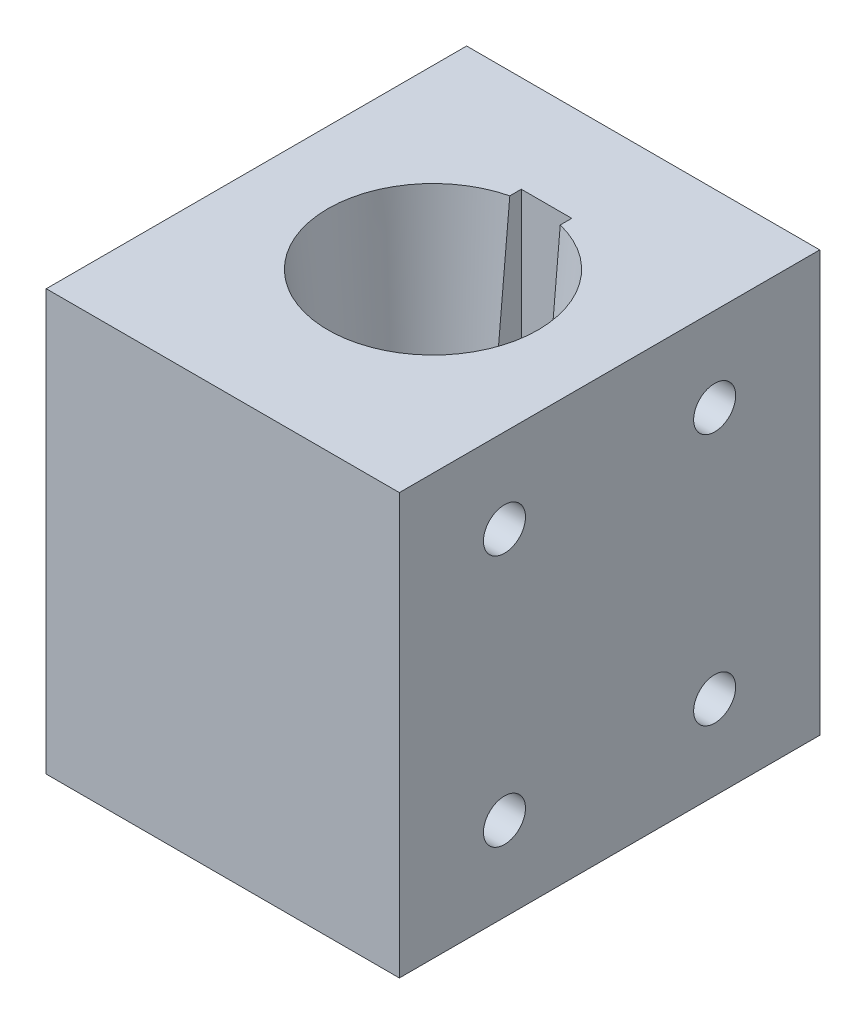
SolidWorks part; units mm, degrees
material "PA38 (3.3206)"
ref_plane "Płaszczyzna przednia" through (0, 0, 0) normal (0, 0, 1) x (1, 0, 0)
ref_plane "Płaszczyzna górna" through (0, 0, 0) normal (0, 1, 0) x (1, 0, 0)
ref_plane "Płaszczyzna prawa" through (0, 0, 0) normal (1, 0, 0) x (0, 0, -1)
sketch "Szkic6" plane through (0, 0, 0) normal (0, 1, 0) x (1, 0, 0)
  line L1 (21, -25) -> (-21, -25)
  line L2 (21, -25) -> (21, 25)
  line L3 (21, 25) -> (-21, 25)
  line L4 (-21, -25) -> (-21, 25)
  line L5 (21, -25) -> (-21, 25) construction
  line L6 (21, 25) -> (-21, -25) construction
  point P0 (0, 0)
  dimension "D1" = 42
  dimension "D2" = 50
extrude "Dodanie-wyciągnięcie3" add sketch "Szkic6" along normal mid plane 50
sketch "Szkic7" plane through (0, 0, 0) normal (1, 0, 0) x (0, 0, -1)
  line L0 (0, 25) -> (0, -25) construction
  line L1 (-25, 25) -> (25, 25) construction
  line L2 (-25, -25) -> (25, -25) construction
  line L3 (0, 25) -> (-12.5, 25)
  line L4 (-12.5, 25) -> (-8.1256, -25)
  line L5 (-8.1256, -25) -> (0, -25)
  line L7 (0, 25) -> (0, -25)
  dimension "D1" = 25
  dimension "D2" = 5
revolve "Wycięcie-obrót1" cut sketch "Szkic7" angle 360 about L0
sketch "Szkic8" plane through (0, 25, 0) normal (0, 1, 0) x (1, 0, 0)
  line L1 (-3, 13.5) -> (3, 13.5)
  line L2 (-3, 13.5) -> (-3, 0)
  line L3 (-3, 0) -> (3, 0)
  line L4 (3, 13.5) -> (3, 0)
  point P5 (0, 0)
  dimension "D1" = 6
  dimension "D2" = 13.5
extrude "Wytnij-wyciągnięcie1" cut sketch "Szkic8" against normal up to next
hole_wizard "Otwór gwintowany M62" positions "Szkic9" profile "Szkic10" tap size "M6" standard "DIN"
sketch "Szkic9" plane through (21, 0, 0) normal (1, 0, 0) x (0, 0, -1)
  line L0 (-12.5, 15) -> (12.5, 15) construction
  line L1 (12.5, 15) -> (12.5, -15) construction
  line L2 (12.5, -15) -> (-12.5, -15) construction
  line L3 (-12.5, -15) -> (-12.5, 15) construction
  line L4 (-12.5, 15) -> (12.5, -15) construction
  point P0 (-12.5, 15)
  point P2 (12.5, 15)
  point P4 (12.5, -15)
  point P6 (-12.5, -15)
  dimension "D1" = 25
  dimension "D2" = 30
sketch "Szkic10" plane through (21, 15, 12.5) normal (0, 1, 0) x (0, 0, -1)
  line L0 (0, 0) -> (0, 14.5022)
  line L1 (0, 14.5022) -> (2.5, 13)
  line L2 (2.5, 13) -> (2.5, 0)
  line L5 (2.5, 0) -> (0, 0)
  line L10 (0, 14.5022) -> (-2.5, 13) construction
  line L11 (0, -6.35) -> (0, 107.95) construction
  dimension "Średnica wiertła gwintu" = 5
  dimension "Głębokość otworu gwintowanego" = 13
  dimension "Kąt wiertła" = 118
cosmetic thread "Gwint otworu3" parameters "D1"=8, "D2"=6
cosmetic thread "Gwint otworu4" parameters "D1"=8, "D2"=6
cosmetic thread "Gwint otworu5" parameters "D1"=8, "D2"=6
cosmetic thread "Gwint otworu6" parameters "D1"=8, "D2"=6
mirror "Lustro2" about plane through (0, 0, 0) normal (1, 0, 0) of "Otwór gwintowany M62"
sketch "Szkic11" plane through (0, -25, 0) normal (0, -1, 0) x (1, 0, 0)
  circle A0 centre (0, 0) radius 12.5
  dimension "D1" = 25
extrude "Wytnij-wyciągnięcie2" cut sketch "Szkic11" against normal blind 12
